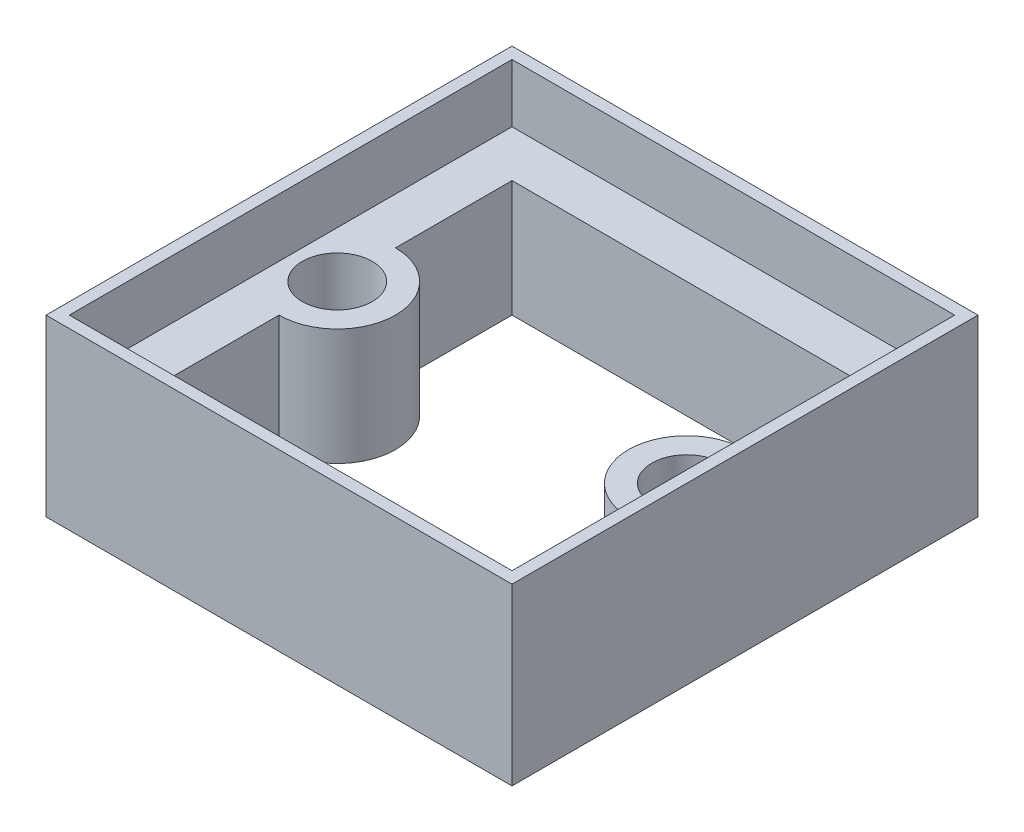
SolidWorks part; units mm, degrees
material "PET"
ref_plane "Front Plane" through (0, 0, 0) normal (0, 0, 1) x (1, 0, 0)
ref_plane "Top Plane" through (0, 0, 0) normal (0, 1, 0) x (1, 0, 0)
ref_plane "Right Plane" through (0, 0, 0) normal (1, 0, 0) x (0, 0, -1)
sketch "Sketch1" plane through (0, 0, 0) normal (0, 1, 0) x (1, 0, 0)
  line L0 (-15, 5) -> (-20, 5)
  line L1 (-20, -20) -> (20, -20)
  line L2 (-20, -20) -> (-20, 20)
  line L3 (-20, 20) -> (20, 20)
  line L4 (20, -20) -> (20, 20)
  line L5 (-20, -20) -> (20, 20) construction
  line L6 (-20, 20) -> (20, -20) construction
  line L7 (-15, -5) -> (-20, -5)
  line L8 (15, 5) -> (20, 5)
  line L9 (15, -5) -> (20, -5)
  line L10 (-15, 15) -> (15, 15)
  line L11 (15, -15) -> (15, 15)
  line L12 (-15, -15) -> (15, -15)
  line L13 (-15, -15) -> (-15, 15)
  circle A0 centre (15, 0) radius 1.5
  circle A1 centre (-15, 0) radius 1.5
  circle A2 centre (-15, 0) radius 3
  circle A3 centre (15, 0) radius 3
  circle A4 centre (15, 0) radius 5
  circle A5 centre (-15, 0) radius 5
  point P0 (0, 0)
  dimension "D3" = 5
  dimension "D1" = 40
  dimension "D2" = 40
extrude "Boss-Extrude2" add sketch "Sketch1" along normal blind 10 contours L12 L13 L7 L2 L1 L4 L9 L11 | L0 L13 L10 L11 L8 L4 L3 L2 | L13 A5 A2 | A5 L0 L2 | A5 L2 L7 | A4 L4 L8 | L11 A4 A3 | A4 L9 L4 | L11 A4 A3 region at (-18.8832, 0, -3.8832) region at (-17.5, 0, -5.4272) region at (-15.1118, 0, -4) region at (-18.8832, 0, 3.8832) region at (-15.4272, 0, 10) region at (18.4565, 0, -3.4565) region at (18.8832, 0, -3.8832) region at (14.8882, 0, -4) region at (18.8832, 0, 3.8832)
extrude "Boss-Extrude3" add sketch "Sketch1<4>" along normal blind 10 contours L13 A5 A2 region at (-11.5435, 0, -3.4565)
sketch "Sketch1<4>" plane through (0, 0, 0) normal (0, 1, 0) x (1, 0, 0) same geometry as "Sketch1"
extrude "Boss-Extrude4" add sketch "Sketch1<5>" along normal blind 2 contours L13 A2 A1 | L13 A2 A1 | L11 A3 A0 | L11 A3 A0 region at (-12.9261, 0, -2.0739) region at (-15.0671, 0, -2.25) region at (17.0739, 0, -2.0739) region at (14.9329, 0, -2.25)
sketch "Sketch1<5>" plane through (0, 0, 0) normal (0, 1, 0) x (1, 0, 0) same geometry as "Sketch1"
sketch "Sketch2" plane through (0, 10, 0) normal (0, 1, 0) x (1, 0, 0)
  line L1 (-19, -19) -> (19, -19)
  line L2 (-19, -19) -> (-19, 19)
  line L3 (-19, 19) -> (19, 19)
  line L4 (19, -19) -> (19, 19)
  line L5 (-19, -19) -> (19, 19) construction
  line L6 (-19, 19) -> (19, -19) construction
  line L7 (-20, -20) -> (20, -20)
  line L8 (-20, -20) -> (-20, 20)
  line L9 (-20, 20) -> (20, 20)
  line L10 (20, -20) -> (20, 20)
  line L11 (-20, -20) -> (20, 20) construction
  line L12 (-20, 20) -> (20, -20) construction
  point P0 (0, 0)
  point P6 (0, 0)
  dimension "D1" = 38
  dimension "D2" = 38
extrude "Boss-Extrude5" add sketch "Sketch2" along normal blind 5
